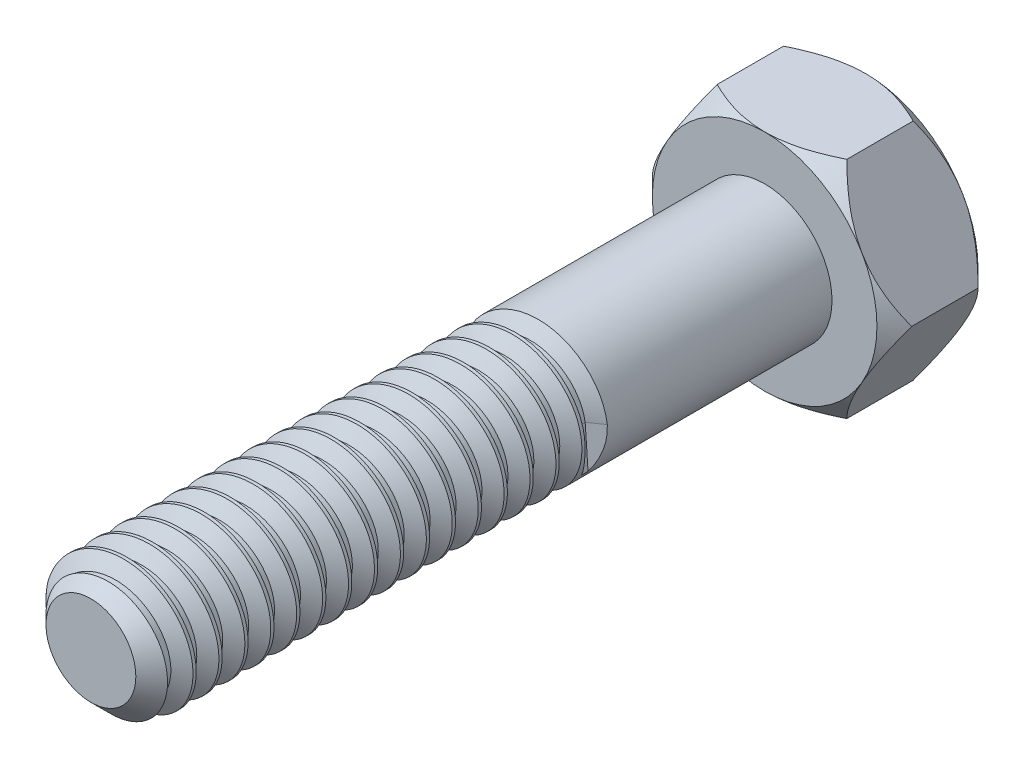
SolidWorks part; units mm, degrees
ref_plane "Front Plane" through (0, 0, 0) normal (0, 0, 1) x (1, 0, 0)
ref_plane "Top Plane" through (0, 0, 0) normal (0, 1, 0) x (1, 0, 0)
ref_plane "Right Plane" through (0, 0, 0) normal (1, 0, 0) x (0, 0, -1)
sketch "Sketch1" plane through (0, 0, 0) normal (0, 0, 1) x (1, 0, 0)
  line L1 (1.4434, -2.5) -> (2.8868, 0)
  line L2 (2.8868, 0) -> (1.4434, 2.5)
  line L3 (1.4434, 2.5) -> (-1.4434, 2.5)
  line L4 (-1.4434, 2.5) -> (-2.8868, 0)
  line L5 (-2.8868, 0) -> (-1.4434, -2.5)
  line L6 (-1.4434, -2.5) -> (1.4434, -2.5)
  circle A0 centre (0, 0) radius 2.5 construction
  dimension "D1" = 5
extrude "Boss-Extrude1" add sketch "Sketch1" along normal mid plane 2.25
sketch "Sketch2" plane through (0, 0, 1.125) normal (0, 0, 1) x (1, 0, 0)
  line L0 (-1.4434, 2.5) -> (-2.8868, 0) construction
  circle A0 centre (0, 0) radius 2.5
extrude "Cut-Extrude1" cut sketch "Sketch2" against normal through all draft 45 flip side to cut contours A0
mirror "Mirror1" about plane through (0, 0, 0) normal (0, 0, 1) of "Cut-Extrude1"
sketch "Sketch3" plane through (0, 0, 1.125) normal (0, 0, 1) x (1, 0, 0)
  circle A0 centre (0, 0) radius 1.5
  dimension "D1" = 3
extrude "Boss-Extrude2" add sketch "Sketch3" along normal blind 15
chamfer "Chamfer1" distance 0.5 angle 45 1 edges at (1.5, 0, 16.125)
thread "Thread1" pitch 0.5773 method cut profile "Thread Profile2" start angle 4, offset 5, length 0, pitch 0.5773, diameter 3
ref_plane "Plane2" through (1.4963, 0.1046, 6.125) normal (0.0698, -0.9976, 0) x (0.9976, 0.0698, 0)
sketch "Thread Profile2" plane through (1.4963, 0.1046, 6.125) normal (0.0698, -0.9976, 0) x (0.9976, 0.0698, 0)
  line L0 (0, 0) -> (0, 0.5773) construction
  line L11 (0, 0) -> (0, 0.5051)
  line L12 (0, 0.5051) -> (-0.3125, 0.3247)
  line L13 (-0.3125, 0.3247) -> (-0.3125, 0.1804)
  line L15 (-0.3125, 0.1804) -> (0, 0)
  line L17 (-0.3125, 0.2526) -> (0, 0.2526) construction
  point P2 (0, 0)
  dimension "Pitch" = 0.5773
  dimension "Profile_Angle" = 60
  dimension "Profile_Land" = 0.1443
  dimension "Profile_Height" = 0.3125
sketch "Sketch13" plane through (0, 0, 0) normal (-0.0698, 0.9976, 0) x (0.9976, 0.0698, 0)
  line L4 (1.5, -6.125) -> (1.1875, -6.3054)
  line L5 (1.1875, -6.3054) -> (1.1875, -6.4497)
  line L6 (1.1875, -6.4497) -> (1.5, -6.6301)
  line L7 (1.5, -6.6301) -> (1.5, -6.125)
  line L8 (1.5, -6.125) -> (1.1875, -6.3054)
  line L9 (1.1875, -6.3054) -> (1.1875, -6.4497)
  line L10 (1.1875, -6.4497) -> (1.5, -6.6301)
  line L11 (1.5, -6.6301) -> (1.5, -6.125)
  dimension "D1" = 0
extrude "Cut-Extrude2" cut sketch "Sketch13" against normal through all
